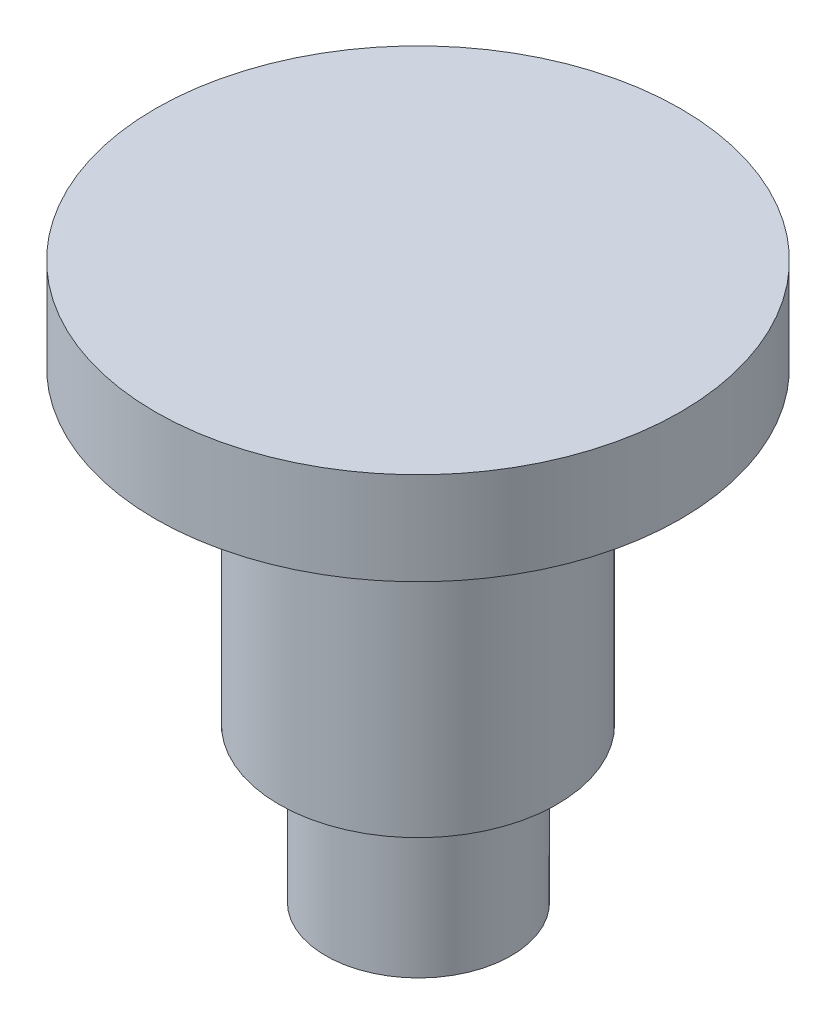
SolidWorks part; units mm, degrees
ref_plane "Front Plane" through (0, 0, 0) normal (0, 0, 1) x (1, 0, 0)
ref_plane "Top Plane" through (0, 0, 0) normal (0, 1, 0) x (1, 0, 0)
ref_plane "Right Plane" through (0, 0, 0) normal (1, 0, 0) x (0, 0, -1)
sketch "Sketch1" plane through (0, 0, 0) normal (0, 1, 0) x (1, 0, 0)
  circle A0 centre (0, 0) radius 4.25
  circle A1 centre (0, 0) radius 2.25
  dimension "D1" = 8.5
  dimension "D2" = 4.5
extrude "Boss-Extrude1" add sketch "Sketch1" along normal blind 1.5 contours A0
extrude "Boss-Extrude2" add sketch "Sketch1<3>" against normal blind 5 contours A1
sketch "Sketch1<3>" plane through (0, 0, 0) normal (0, 1, 0) x (1, 0, 0) same geometry as "Sketch1"
sketch3d "3DSketch1"
  line L0 (2.25, -5, -0.0075) -> (2.25, -5, 12.4925)
  line L1 (2.25, -5, -0.0075) -> (2.25, -7.5, -0.0075)
  line L2 (2.25, -5, -0.0075) -> (2.25, -5, -12.5075)
  line L3 (2.25, -5, -0.0075) -> (-2.25, -5, -0.0075)
  circle A0 centre (0, -5, 0) radius 2.25 construction
  spline S0 degree 2 poles (2.25, -5, -12.5075) (2.25, -10, -0.0075) (2.25, -5, 12.4925) knots 0 0 0 1 1 1
  point P2 (0, -2.75, 0)
  dimension "D1" = 12.5
  dimension "D2" = 2.5
  dimension "D3" = 12.5
sketch "Sketch2" plane through (0, -5, 0) normal (0, -1, 0) x (1, 0, 0)
  line L0 (2.25, -0.0075) -> (-2.25, -0.0075) construction
  circle A0 centre (0, -0.0075) radius 1.5
  dimension "D1" = 3
extrude "Boss-Extrude3" add sketch "Sketch2" along normal blind 2.5
